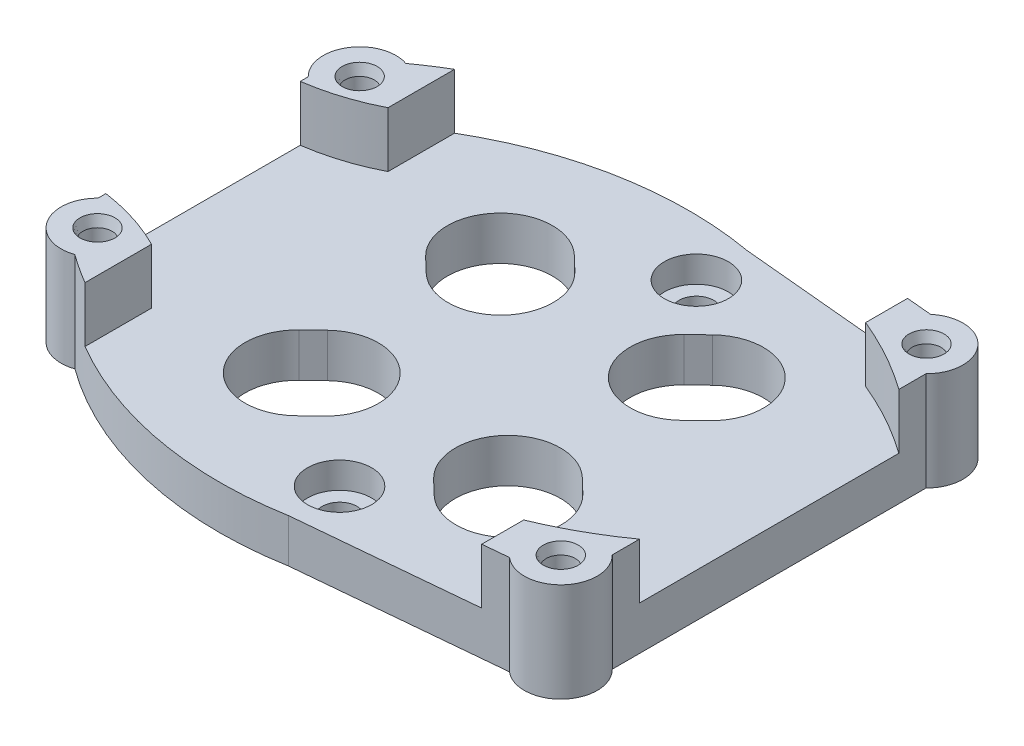
SolidWorks part; units mm, degrees
ref_plane "Front Plane" through (0, 0, 0) normal (0, 0, 1) x (1, 0, 0)
ref_plane "Top Plane" through (0, 0, 0) normal (0, 1, 0) x (1, 0, 0)
ref_plane "Right Plane" through (0, 0, 0) normal (1, 0, 0) x (0, 0, -1)
sketch "Sketch1" plane through (0, 0, 0) normal (0, 1, 0) x (1, 0, 0)
  line L0 (36.956, -25.685) -> (40.3201, -38.24) construction
  line L1 (36.956, -25.685) -> (46.656, -25.685) construction
  line L2 (24.8242, -41.435) -> (40.3201, -39.99)
  line L3 (42.0701, -13.13) -> (42.0701, -38.24)
  line L4 (36.956, -25.685) -> (4.956, -25.685) construction
  line L5 (4.956, -25.685) -> (4.956, -34.685) construction
  line L6 (7.7835, -33.245) -> (7.7835, -38.37)
  line L7 (3.206, -16.685) -> (3.206, -34.685)
  line L8 (36.956, -36.8813) -> (36.956, -40.3037)
  line L9 (36.956, -14.4887) -> (36.956, -11.0663)
  line L10 (24.8242, -9.935) -> (40.3201, -11.38)
  line L11 (7.7835, -18.125) -> (7.7835, -13)
  arc A8 (24.8242, -41.435) -> (25.4713, -41.3746) centre (24.8242, -37.935) ccw
  arc A13 (40.3201, -39.99) -> (42.0701, -38.24) centre (40.3201, -38.24) ccw
  arc A14 (4.956, -36.435) -> (24.8242, -41.435) centre (20.4556, -16.8196) ccw
  arc A15 (3.206, -34.685) -> (4.956, -36.435) centre (4.956, -34.685) ccw
  circle A16 centre (4.956, -34.685) radius 1
  circle A17 centre (40.3201, -38.24) radius 1
  circle A18 centre (24.8242, -37.935) radius 1
  arc A19 (36.956, -36.8813) -> (42.0701, -33.9697) centre (27.2302, -13.8507) ccw
  arc A20 (7.7835, -33.245) -> (3.206, -31.8522) centre (1.1844, -46.7154) ccw
  circle A21 centre (40.3201, -13.13) radius 1
  arc A22 (36.956, -14.4887) -> (42.0701, -17.4002) centre (27.2302, -37.5193) cw
  arc A23 (40.3201, -11.38) -> (42.0701, -13.13) centre (40.3201, -13.13) cw
  circle A24 centre (24.8242, -13.435) radius 1
  arc A25 (4.956, -14.935) -> (24.8242, -9.935) centre (20.4556, -34.5503) cw
  arc A26 (3.206, -16.685) -> (4.956, -14.935) centre (4.956, -16.685) cw
  circle A27 centre (4.956, -16.685) radius 1
  arc A28 (7.7835, -18.125) -> (3.206, -19.5177) centre (1.1844, -4.6546) cw
  arc A29 (4.956, -32.185) -> (4.91, -32.1854) centre (4.956, -34.685) ccw
  arc A30 (5.7673, -14.3203) -> (3.206, -18.4703) centre (4.956, -16.685) ccw
  arc A31 (3.206, -32.8996) -> (5.7673, -37.0497) centre (4.956, -34.685) ccw
  arc A32 (38.6969, -40.1414) -> (42.0701, -36.4546) centre (40.3201, -38.24) ccw
  arc A33 (42.0701, -14.9153) -> (38.6969, -11.2286) centre (40.3201, -13.13) ccw
  point P11 (42.0701, -25.685)
  point P50 (3.206, -25.685)
  dimension "D1" = 7
  dimension "D2" = 3.5
  dimension "D5" = 3.5
  dimension "D8" = 25
  dimension "D11" = 2
  dimension "D12" = 24.5
  dimension "D13" = 17.2459
  dimension "D14" = 2.8275
  dimension "D9" = 2
  dimension "D10" = 2
  dimension "D16" = 25
  dimension "D17" = 15
  dimension "D22" = 5
  dimension "D23" = 5
  dimension "D24" = 5
  dimension "D25" = 5
  dimension "D3" = 75
  dimension "D4" = 25.11
  dimension "D6" = 32
  dimension "D7" = 9
  dimension "D15" = 9.7
  dimension "D18" = 4.2703
  dimension "D19" = 3.4224
  dimension "D20" = 5.125
  dimension "D21" = 2.8327
extrude "Boss-Extrude1" add sketch "Sketch1" along normal blind 3 contours L11 A28 L7 A20 L6 A14 L2 L8 A19 L3 A22 L9 L10 A25 A18 A24 | A28 L11 A25 A26 L7 A27 | L6 A20 L7 A15 A14 A16 | A23 L10 L9 A22 L3 A21 | A19 L8 L2 A13 L3 A17 | L7 A31 A14 A15 | A25 A30 L7 A26 | L2 A32 L3 A13 | L3 A33 L10 A23 region at (23.1035, 0, 25.685) region at (6.8031, 0, 37.6675) region at (37.0374, 0, 38.5925) region at (2.8746, 0, 35.9696) region at (39.514, 0, 40.1249) region at (39.6393, 0, 15.7227) region at (3.2856, 0, 18.994) region at (42.1296, 0, 14.0227) region at (2.8746, 0, 15.4004)
extrude "Boss-Extrude2" add sketch "Sketch1<5>" along normal blind 6.8 contours L6 A20 L7 A15 A14 A16 | A23 L10 L9 A22 L3 A21 | A28 L11 A25 A26 L7 A27 | A19 L8 L2 A13 L3 A17 | A25 A30 L7 A26 | L7 A31 A14 A15 | L3 A33 L10 A23 | L2 A32 L3 A13 region at (6.8031, 0, 37.6675) region at (37.0374, 0, 38.5925) region at (2.8746, 0, 35.9696) region at (39.514, 0, 40.1249) region at (39.6393, 0, 15.7227) region at (3.2856, 0, 18.994) region at (42.1296, 0, 14.0227) region at (2.8746, 0, 15.4004)
sketch "Sketch1<5>" plane through (0, 0, 0) normal (0, 1, 0) x (1, 0, 0) same geometry as "Sketch1"
sketch "Sketch2" plane through (0, 3, 0) normal (0, 1, 0) x (1, 0, 0)
  line L8 (16.6451, -32.6328) -> (31.1244, -18.7372) construction
  line L9 (31.1261, -32.631) -> (16.6433, -18.739) construction
  line L10 (23.8847, -37.935) -> (23.8847, -13.435) construction
  line L12 (16.6451, -32.6328) -> (17.6335, -31.6842) construction
  line L13 (15.5303, -31.4712) -> (16.5187, -30.5226)
  line L14 (17.7599, -33.7944) -> (18.7483, -32.8458)
  line L15 (17.632, -19.6874) -> (16.6433, -18.739) construction
  line L16 (16.5175, -20.8493) -> (15.5288, -19.9009)
  line L17 (18.7465, -18.5255) -> (17.7578, -17.5771)
  line L18 (31.1244, -32.6328) -> (30.1359, -31.6842) construction
  line L19 (32.2392, -31.4712) -> (31.2507, -30.5226)
  line L20 (30.0096, -33.7944) -> (29.0211, -32.8458)
  line L21 (30.1375, -19.6874) -> (31.1261, -18.739) construction
  line L22 (31.2519, -20.8493) -> (32.2406, -19.9009)
  line L23 (29.023, -18.5255) -> (30.0117, -17.5771)
  line L24 (14.1455, -30.0282) -> (15.1339, -29.0796)
  line L25 (19.1447, -35.2374) -> (20.1331, -34.2888)
  line L26 (15.133, -22.2926) -> (14.1443, -21.3443)
  line L27 (20.1309, -17.0821) -> (19.1422, -16.1338)
  line L28 (32.6364, -22.2926) -> (33.6251, -21.3443)
  line L29 (27.6385, -17.0821) -> (28.6272, -16.1338)
  line L30 (33.624, -30.0282) -> (32.6355, -29.0796)
  line L31 (28.6247, -35.2374) -> (27.6363, -34.2888)
  line L32 (24.8242, -37.935) -> (24.8242, -36.935) construction
  arc A9 (15.5303, -31.4712) -> (17.7599, -33.7944) centre (16.6451, -32.6328) ccw
  arc A10 (18.7483, -32.8458) -> (16.5187, -30.5226) centre (17.6335, -31.6842) ccw
  arc A11 (16.5175, -20.8493) -> (18.7465, -18.5255) centre (17.632, -19.6874) ccw
  arc A12 (17.7578, -17.5771) -> (15.5288, -19.9009) centre (16.6433, -18.739) ccw
  arc A13 (32.2392, -31.4712) -> (30.0096, -33.7944) centre (31.1244, -32.6328) cw
  arc A14 (29.0211, -32.8458) -> (31.2507, -30.5226) centre (30.1359, -31.6842) cw
  arc A15 (31.2519, -20.8493) -> (29.023, -18.5255) centre (30.1375, -19.6874) cw
  arc A16 (30.0117, -17.5771) -> (32.2406, -19.9009) centre (31.1261, -18.739) cw
  arc A17 (20.1331, -34.2888) -> (15.1339, -29.0796) centre (17.6335, -31.6842) ccw
  arc A18 (14.1455, -30.0282) -> (19.1447, -35.2374) centre (16.6451, -32.6328) ccw
  arc A19 (19.1422, -16.1338) -> (14.1443, -21.3443) centre (16.6433, -18.739) ccw
  arc A20 (15.133, -22.2926) -> (20.1309, -17.0821) centre (17.632, -19.6874) ccw
  arc A21 (28.6272, -16.1338) -> (33.6251, -21.3443) centre (31.1261, -18.739) cw
  arc A22 (32.6364, -22.2926) -> (27.6385, -17.0821) centre (30.1375, -19.6874) cw
  arc A23 (27.6363, -34.2888) -> (32.6355, -29.0796) centre (30.1359, -31.6842) cw
  arc A24 (33.624, -30.0282) -> (28.6247, -35.2374) centre (31.1244, -32.6328) cw
  circle A25 centre (24.8242, -37.935) radius 1 construction
  point P3 (30.6301, -32.1585)
  point P4 (17.1376, -19.2132)
  point P13 (23.8847, -25.685)
  point P21 (30.6318, -19.2132)
  point P27 (23.8847, -25.685)
  point P29 (23.8847, -25.685)
  point P34 (17.1393, -32.1585)
  dimension "D4" = 12.9453
  dimension "D12" = 1.37
  dimension "D13" = 1.61
  dimension "D2" = 92.371
  dimension "D3" = 2
  dimension "D5" = 13.4942
  dimension "D6" = 24.5
  dimension "D7" = 0.9394
extrude "Cut-Extrude1" cut sketch "Sketch2" against normal blind 7 contours L26 A20 L27 A19 A12 L17 A11 L16 | A22 L28 A21 L29 L23 A16 L22 A15 | A16 L23 A15 L22 | A24 L30 A23 L31 L20 A14 L19 A13 | A14 L20 A13 L19 | L24 A18 L25 A17 A10 L14 A9 L13 | L14 A10 L13 A9 | L17 A12 L16 A11 region at (17.1393, 3, 32.1585) region at (30.6301, 3, 32.1585) region at (30.6318, 3, 19.2132) region at (14.7199, 3, 29.6374) region at (14.7189, 3, 21.7349) region at (27.6158, 3, 22.1062) region at (33.6454, 3, 35.0522)
sketch "Sketch3" plane through (0, 3, 0) normal (0, 1, 0) x (1, 0, 0)
  circle A0 centre (24.8242, -13.435) radius 2
  circle A1 centre (24.8242, -37.935) radius 2
  dimension "D1" = 4
extrude "Cut-Extrude2" cut sketch "Sketch3" against normal blind 1.8
other "Move Face1" flip direction yes face at (39.556, 4.9, 35.501) face at (39.556, 4.9, 15.869) face at (5.5227, 4.9, 18.9132) face at (5.5227, 4.9, 32.4568) offset 0.5 parameters "D1"=0.5
other "Move Face2" flip direction yes face at (24.8242, 1.2, 15.435) face at (24.8242, 1.2, 39.935) face at (24.8242, 0, 14.435) face at (24.8242, 0, 38.935) offset 0.2 parameters "D1"=0.2
chamfer "Chamfer1" distance 0.7 distance2 0.2 2 edges at (4.956, 6.8, 17.685) (40.3201, 6.8, 14.13) first distance on face at (4.956, 0, 17.685) first distance on face at (40.3201, 0, 14.13)
chamfer "Chamfer2" distance 0.2 distance2 0.7 2 edges at (40.3201, 6.8, 39.24) (4.956, 6.8, 35.685) first distance on face at (39.7223, 6.8, 38.1374) first distance on face at (4.956, 6.8, 35.685)
